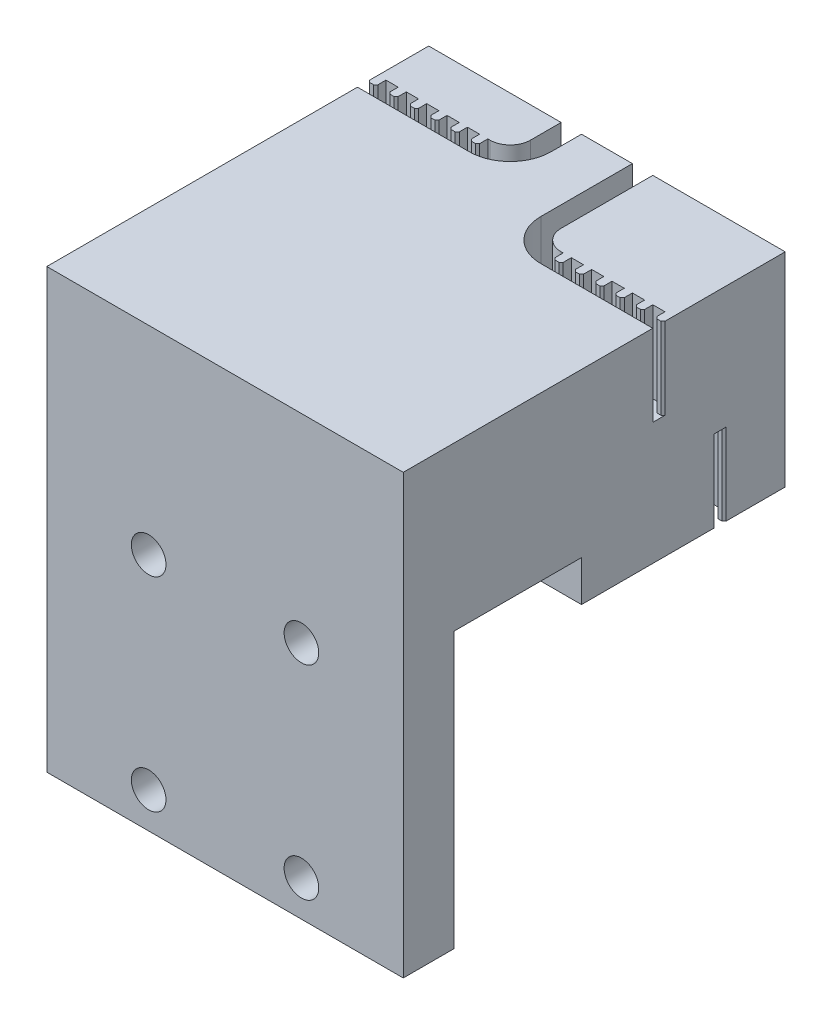
SolidWorks part; units mm, degrees
ref_plane "Front Plane" through (0, 0, 0) normal (0, 0, 1) x (1, 0, 0)
ref_plane "Top Plane" through (0, 0, 0) normal (0, 1, 0) x (1, 0, 0)
ref_plane "Right Plane" through (0, 0, 0) normal (1, 0, 0) x (0, 0, -1)
sketch "Sketch1" plane through (0, 0, 0) normal (0, 1, 0) x (1, 0, 0)
  line L1 (0, 0) -> (35, 0)
  line L2 (0, 0) -> (0, 20)
  line L3 (0, 20) -> (35, 20)
  line L4 (35, 0) -> (35, 20)
  dimension "D1" = 20
  dimension "D2" = 35
extrude "Boss-Extrude1" add sketch "Sketch1" along normal blind 20
sketch "Sketch2" plane through (0, 20, 0) normal (0, 1, 0) x (1, 0, 0)
  line L0 (0, 13) -> (11, 13)
  line L1 (0, 20) -> (0, 0) construction
  line L2 (15, 17) -> (15, 20)
  line L3 (35, 20) -> (0, 20) construction
  line L4 (0, 15) -> (11, 15)
  line L5 (13, 17) -> (13, 20)
  line L6 (35, 7) -> (24, 7)
  line L7 (35, 0) -> (35, 20) construction
  line L8 (20, 11) -> (20, 20)
  line L9 (0, 0) -> (35, 0) construction
  line L10 (22, 20) -> (22, 11)
  line L11 (24, 9) -> (35, 9)
  line L12 (35, 9) -> (35, 7)
  line L13 (0, 13) -> (0, 15)
  line L14 (13, 20) -> (15, 20)
  line L15 (20, 20) -> (22, 20)
  arc A0 (15, 17) -> (11, 13) centre (11, 17) cw
  arc A1 (13, 17) -> (11, 15) centre (11, 17) cw
  arc A2 (20, 11) -> (24, 7) centre (24, 11) ccw
  arc A3 (22, 11) -> (24, 9) centre (24, 11) ccw
  point P9 (15, 13)
  point P15 (13, 15)
  point P29 (20, 7)
  point P32 (22, 9)
  dimension "D3" = 4
  dimension "D6" = 2
  dimension "D11" = 4
  dimension "D12" = 2
  dimension "D1" = 15
  dimension "D2" = 7
  dimension "D4" = 5
  dimension "D5" = 13
  dimension "D7" = 15
  dimension "D8" = 7
  dimension "D9" = 13
  dimension "D10" = 2
extrude "Cut-Extrude1" cut sketch "Sketch2" against normal blind 8
sketch "Sketch5" plane through (0, 0, 0) normal (0, -1, 0) x (-1, 0, 0)
  line L0 (-35, 13) -> (-24, 13)
  line L2 (-20, 17) -> (-20, 20)
  line L4 (-35, 15) -> (-24, 15)
  line L5 (-22, 17) -> (-22, 20)
  line L6 (0, 7) -> (-11, 7)
  line L8 (-15, 11) -> (-15, 20)
  line L10 (-13, 20) -> (-13, 11)
  line L11 (-11, 9) -> (0, 9)
  line L12 (0, 9) -> (0, 7)
  line L13 (-35, 13) -> (-35, 15)
  line L14 (-22, 20) -> (-20, 20)
  line L15 (-15, 20) -> (-13, 20)
  line L16 (-35, 0) -> (-35, 20) construction
  line L17 (-35, 20) -> (0, 20) construction
  line L18 (0, 20) -> (0, 0) construction
  line L19 (0, 0) -> (-35, 0) construction
  arc A0 (-20, 17) -> (-24, 13) centre (-24, 17) cw
  arc A1 (-22, 17) -> (-24, 15) centre (-24, 17) cw
  arc A2 (-15, 11) -> (-11, 7) centre (-11, 11) ccw
  arc A3 (-13, 11) -> (-11, 9) centre (-11, 11) ccw
  point P9 (-20, 13)
  point P15 (-22, 15)
  point P29 (-15, 7)
  point P32 (-13, 9)
  dimension "D3" = 4
  dimension "D6" = 2
  dimension "D11" = 4
  dimension "D12" = 2
  dimension "D1" = 15
  dimension "D2" = 7
  dimension "D4" = 5
  dimension "D5" = 13
  dimension "D7" = 15
  dimension "D8" = 0
  dimension "D9" = 13
  dimension "D10" = 2
  dimension "D13" = 0
  dimension "D14" = 0
  dimension "D15" = 0
  dimension "D16" = 7
extrude "Cut-Extrude2" cut sketch "Sketch5" against normal blind 8
sketch "Sketch6" plane through (0, 20, 0) normal (0, 1, 0) x (1, 0, 0)
  line L0 (0.2, 14) -> (0, 14.2)
  line L1 (0, 15) -> (0.8, 15)
  line L2 (0, 15) -> (0, 14.2)
  line L3 (0.2, 14) -> (0.6, 14)
  line L4 (0.8, 15) -> (0.8, 14.2)
  line L5 (0.6, 14) -> (0.8, 14.2)
  line L6 (2.2, 14) -> (2, 14.2)
  line L7 (2, 15) -> (2.8, 15)
  line L8 (2, 15) -> (2, 14.2)
  line L9 (2.2, 14) -> (2.6, 14)
  line L10 (2.8, 15) -> (2.8, 14.2)
  line L11 (2.6, 14) -> (2.8, 14.2)
  line L12 (4.2, 14) -> (4, 14.2)
  line L13 (4, 15) -> (4.8, 15)
  line L14 (4, 15) -> (4, 14.2)
  line L15 (4.2, 14) -> (4.6, 14)
  line L16 (4.8, 15) -> (4.8, 14.2)
  line L17 (4.6, 14) -> (4.8, 14.2)
  line L18 (6.2, 14) -> (6, 14.2)
  line L19 (6, 15) -> (6.8, 15)
  line L20 (6, 15) -> (6, 14.2)
  line L21 (6.2, 14) -> (6.6, 14)
  line L22 (6.8, 15) -> (6.8, 14.2)
  line L23 (6.6, 14) -> (6.8, 14.2)
  line L24 (8.2, 14) -> (8, 14.2)
  line L25 (8, 15) -> (8.8, 15)
  line L26 (8, 15) -> (8, 14.2)
  line L27 (8.2, 14) -> (8.6, 14)
  line L28 (8.8, 15) -> (8.8, 14.2)
  line L29 (8.6, 14) -> (8.8, 14.2)
  line L30 (10.2, 14) -> (10, 14.2)
  line L31 (10, 15) -> (10.8, 15)
  line L32 (10, 15) -> (10, 14.2)
  line L33 (10.2, 14) -> (10.6, 14)
  line L34 (10.8, 15) -> (10.8, 14.2)
  line L35 (10.6, 14) -> (10.8, 14.2)
  line L36 (34.4, 8) -> (34.2, 8.2)
  line L37 (34.2, 9) -> (35, 9)
  line L38 (34.2, 9) -> (34.2, 8.2)
  line L39 (34.4, 8) -> (34.8, 8)
  line L40 (35, 9) -> (35, 8.2)
  line L41 (34.8, 8) -> (35, 8.2)
  line L42 (35, 9) -> (24, 9) construction
  line L43 (35, 7) -> (35, 9) construction
  line L44 (32.4, 8) -> (32.2, 8.2)
  line L45 (32.2, 9) -> (33, 9)
  line L46 (32.2, 9) -> (32.2, 8.2)
  line L47 (32.4, 8) -> (32.8, 8)
  line L48 (33, 9) -> (33, 8.2)
  line L49 (32.8, 8) -> (33, 8.2)
  line L50 (30.4, 8) -> (30.2, 8.2)
  line L51 (30.2, 9) -> (31, 9)
  line L52 (30.2, 9) -> (30.2, 8.2)
  line L53 (30.4, 8) -> (30.8, 8)
  line L54 (31, 9) -> (31, 8.2)
  line L55 (30.8, 8) -> (31, 8.2)
  line L56 (28.4, 8) -> (28.2, 8.2)
  line L57 (28.2, 9) -> (29, 9)
  line L58 (28.2, 9) -> (28.2, 8.2)
  line L59 (28.4, 8) -> (28.8, 8)
  line L60 (29, 9) -> (29, 8.2)
  line L61 (28.8, 8) -> (29, 8.2)
  line L62 (26.4, 8) -> (26.2, 8.2)
  line L63 (26.2, 9) -> (27, 9)
  line L64 (26.2, 9) -> (26.2, 8.2)
  line L65 (26.4, 8) -> (26.8, 8)
  line L66 (27, 9) -> (27, 8.2)
  line L67 (26.8, 8) -> (27, 8.2)
  line L68 (24.4, 8) -> (24.2, 8.2)
  line L69 (24.2, 9) -> (25, 9)
  line L70 (24.2, 9) -> (24.2, 8.2)
  line L71 (24.4, 8) -> (24.8, 8)
  line L72 (25, 9) -> (25, 8.2)
  line L73 (24.8, 8) -> (25, 8.2)
  dimension "D1" = 6
  dimension "D2" = 0.8
  dimension "D3" = 0.8
  dimension "D4" = 0
  dimension "D5" = 0
  dimension "D6" = 6
extrude "Boss-Extrude2" add sketch "Sketch6" against normal blind 8
sketch "Sketch8" plane through (0, 0, 0) normal (0, -1, 0) x (1, 0, 0)
  line L0 (34.8, -14) -> (35, -14.2)
  line L1 (35, -15) -> (34.2, -15)
  line L2 (35, -15) -> (35, -14.2)
  line L3 (34.8, -14) -> (34.4, -14)
  line L4 (34.2, -15) -> (34.2, -14.2)
  line L5 (34.4, -14) -> (34.2, -14.2)
  line L6 (32.8, -14) -> (33, -14.2)
  line L7 (33, -15) -> (32.2, -15)
  line L8 (33, -15) -> (33, -14.2)
  line L9 (32.8, -14) -> (32.4, -14)
  line L10 (32.2, -15) -> (32.2, -14.2)
  line L11 (32.4, -14) -> (32.2, -14.2)
  line L12 (30.8, -14) -> (31, -14.2)
  line L13 (31, -15) -> (30.2, -15)
  line L14 (31, -15) -> (31, -14.2)
  line L15 (30.8, -14) -> (30.4, -14)
  line L16 (30.2, -15) -> (30.2, -14.2)
  line L17 (30.4, -14) -> (30.2, -14.2)
  line L18 (28.8, -14) -> (29, -14.2)
  line L19 (29, -15) -> (28.2, -15)
  line L20 (29, -15) -> (29, -14.2)
  line L21 (28.8, -14) -> (28.4, -14)
  line L22 (28.2, -15) -> (28.2, -14.2)
  line L23 (28.4, -14) -> (28.2, -14.2)
  line L24 (26.8, -14) -> (27, -14.2)
  line L25 (27, -15) -> (26.2, -15)
  line L26 (27, -15) -> (27, -14.2)
  line L27 (26.8, -14) -> (26.4, -14)
  line L28 (26.2, -15) -> (26.2, -14.2)
  line L29 (26.4, -14) -> (26.2, -14.2)
  line L30 (24.8, -14) -> (25, -14.2)
  line L31 (25, -15) -> (24.2, -15)
  line L32 (25, -15) -> (25, -14.2)
  line L33 (24.8, -14) -> (24.4, -14)
  line L34 (24.2, -15) -> (24.2, -14.2)
  line L35 (24.4, -14) -> (24.2, -14.2)
  line L36 (0.8, -8.2) -> (0.6, -8)
  line L37 (0, -9) -> (0.8, -9)
  line L38 (0, -9) -> (0, -8.2)
  line L39 (0.2, -8) -> (0.6, -8)
  line L40 (0.8, -9) -> (0.8, -8.2)
  line L41 (0.2, -8) -> (0, -8.2)
  line L42 (2.8, -8.2) -> (2.6, -8)
  line L43 (2, -9) -> (2.8, -9)
  line L44 (2, -9) -> (2, -8.2)
  line L45 (2.2, -8) -> (2.6, -8)
  line L46 (2.8, -9) -> (2.8, -8.2)
  line L47 (2.2, -8) -> (2, -8.2)
  line L48 (4.8, -8.2) -> (4.6, -8)
  line L49 (4, -9) -> (4.8, -9)
  line L50 (4, -9) -> (4, -8.2)
  line L51 (4.2, -8) -> (4.6, -8)
  line L52 (4.8, -9) -> (4.8, -8.2)
  line L53 (4.2, -8) -> (4, -8.2)
  line L54 (6.8, -8.2) -> (6.6, -8)
  line L55 (6, -9) -> (6.8, -9)
  line L56 (6, -9) -> (6, -8.2)
  line L57 (6.2, -8) -> (6.6, -8)
  line L58 (6.8, -9) -> (6.8, -8.2)
  line L59 (6.2, -8) -> (6, -8.2)
  line L60 (8.8, -8.2) -> (8.6, -8)
  line L61 (8, -9) -> (8.8, -9)
  line L62 (8, -9) -> (8, -8.2)
  line L63 (8.2, -8) -> (8.6, -8)
  line L64 (8.8, -9) -> (8.8, -8.2)
  line L65 (8.2, -8) -> (8, -8.2)
  line L66 (10.8, -8.2) -> (10.6, -8)
  line L67 (10, -9) -> (10.8, -9)
  line L68 (10, -9) -> (10, -8.2)
  line L69 (10.2, -8) -> (10.6, -8)
  line L70 (10.8, -9) -> (10.8, -8.2)
  line L71 (10.2, -8) -> (10, -8.2)
  dimension "D2" = 0.8
  dimension "D3" = 0.8
  dimension "D4" = 0.8
  dimension "D5" = 0.8
extrude "Boss-Extrude4" add sketch "Sketch8" against normal blind 8
sketch "Sketch9" plane through (0, 0, 0) normal (0, 0, 1) x (1, 0, 0)
  line L1 (0, 20) -> (35, 20)
  line L2 (0, 20) -> (0, 4)
  line L3 (0, 4) -> (35, 4)
  line L4 (35, 20) -> (35, 4)
  line L5 (35, 20) -> (35, 0) construction
  dimension "D1" = 16
  dimension "D2" = 35
extrude "Boss-Extrude5" add sketch "Sketch9" along normal blind 12.5
sketch "Sketch11" plane through (0, 0, 12.5) normal (0, 0, 1) x (1, 0, 0)
  line L1 (0, 20) -> (35, 20)
  line L2 (0, 20) -> (0, -23)
  line L3 (0, -23) -> (35, -23)
  line L4 (35, 20) -> (35, -23)
  dimension "D1" = 43
  dimension "D2" = 35
extrude "Boss-Extrude6" add sketch "Sketch11" along normal blind 5
sketch "Sketch12" plane through (0, 0, 17.5) normal (0, 0, 1) x (1, 0, 0)
  line L0 (0, 20) -> (0, -23) construction
  line L1 (0, -23) -> (35, -23) construction
  circle A0 centre (10, 0.5) radius 1.7
  circle A1 centre (25, 0.5) radius 1.7
  circle A2 centre (25, -19.5) radius 1.7
  circle A3 centre (10, -19.5) radius 1.7
  point P0 (17.5, -9.5)
  dimension "D3" = 3.4
  dimension "D4" = 7.5
  dimension "D1" = 17.5
  dimension "D2" = 13.5
  dimension "D5" = 10
  dimension "D6" = 2
extrude "Cut-Extrude3" cut sketch "Sketch12" against normal blind 5
